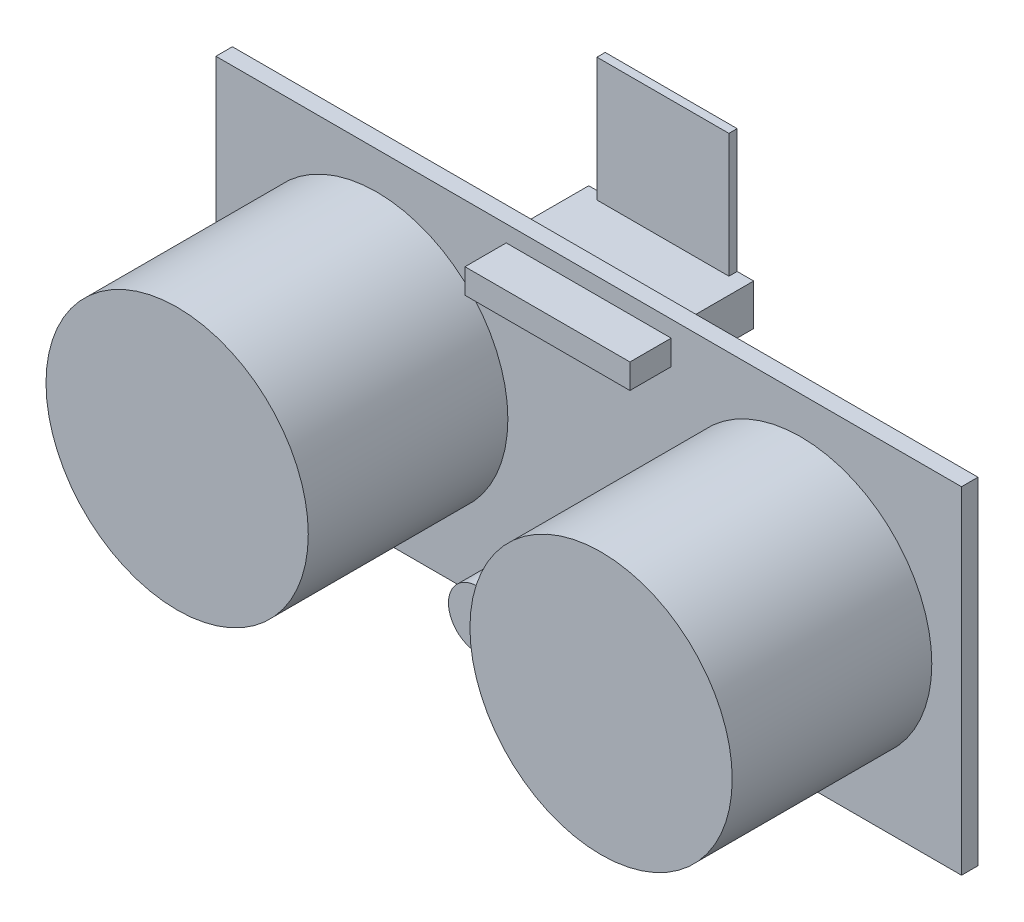
SolidWorks part; units mm, degrees
ref_plane "Plano frontal" through (0, 0, 0) normal (0, 0, 1) x (1, 0, 0)
ref_plane "Plano superior" through (0, 0, 0) normal (0, 1, 0) x (1, 0, 0)
ref_plane "Plano direito" through (0, 0, 0) normal (1, 0, 0) x (0, 0, -1)
sketch "Esboço1" plane through (0, 0, 0) normal (0, 0, 1) x (1, 0, 0)
  line L1 (0, 0) -> (45.2, 0)
  line L2 (0, 0) -> (0, 20.4)
  line L3 (0, 20.4) -> (45.2, 20.4)
  line L4 (45.2, 0) -> (45.2, 20.4)
  dimension "D1" = 20.4
  dimension "D2" = 45.2
extrude "Ressalto-extrusão1" add sketch "Esboço1" along normal blind 1
sketch "Esboço2" plane through (0, 0, 1) normal (0, 0, 1) x (1, 0, 0)
  line L0 (22.6, 20.4) -> (22.6, 0) construction
  line L1 (45.2, 20.4) -> (0, 20.4) construction
  line L2 (0, 0) -> (45.2, 0) construction
  circle A0 centre (9.75, 10.2) radius 7.95
  circle A1 centre (35.45, 10.2) radius 7.95
  dimension "D1" = 15.9
  dimension "D2" = 12.85
  dimension "D3" = 10.2
extrude "Ressalto-extrusão2" add sketch "Esboço2" along normal blind 12.1
sketch "Esboço3" plane through (0, 0, 1) normal (0, 0, 1) x (1, 0, 0)
  line L0 (22.6, 20.4) -> (22.6, 0) construction
  line L1 (45.2, 20.4) -> (0, 20.4) construction
  line L2 (0, 0) -> (45.2, 0) construction
  line L3 (45.2, 10.2) -> (0, 10.2) construction
  line L6 (27.6, 0.5) -> (17.6, 0.5)
  line L7 (27.6, 0.5) -> (27.6, 4)
  line L8 (27.6, 4) -> (17.6, 4)
  line L9 (17.6, 0.5) -> (17.6, 4)
  line L10 (27.6, 0.5) -> (17.6, 4) construction
  line L11 (27.6, 4) -> (17.6, 0.5) construction
  line L12 (45.2, 0) -> (45.2, 20.4) construction
  line L13 (0, 20.4) -> (0, 0) construction
  point P6 (22.6, 2.25)
  dimension "D1" = 10
  dimension "D2" = 3.5
  dimension "D3" = 4
  dimension "D4" = 7.95
extrude "Ressalto-extrusão3" add sketch "Esboço3" along normal blind 3.5
fillet "Filete1" radius 1.75 4 edges at (27.6, 0.5, 2.75) (27.6, 4, 2.75) (17.6, 4, 2.75) (17.6, 0.5, 2.75)
sketch "Esboço4" plane through (0, 0, 0) normal (0, 0, -1) x (-1, 0, 0)
  line L0 (-22.6, 20.4) -> (-22.6, 0) construction
  line L1 (-45.2, 20.4) -> (0, 20.4) construction
  line L2 (0, 0) -> (-45.2, 0) construction
  line L4 (-27.6, 19.9014) -> (-17.6, 19.9014)
  line L5 (-27.6, 19.9014) -> (-27.6, 17.4014)
  line L6 (-27.6, 17.4014) -> (-17.6, 17.4014)
  line L7 (-17.6, 19.9014) -> (-17.6, 17.4014)
  line L8 (-27.6, 19.9014) -> (-17.6, 17.4014) construction
  line L9 (-27.6, 17.4014) -> (-17.6, 19.9014) construction
  point P6 (-22.6, 18.6514)
  dimension "D1" = 10
  dimension "D2" = 2.5
  dimension "D3" = 2.9986
extrude "Ressalto-extrusão4" add sketch "Esboço4" along normal blind 4
sketch "Esboço5" plane through (0, 19.9014, 0) normal (0, 1, 0) x (1, 0, 0)
  line L0 (22.6, 4) -> (22.6, 0) construction
  line L1 (17.6, 4) -> (27.6, 4) construction
  line L2 (45.2, 0) -> (0, 0) construction
  line L4 (18.6, 3.5) -> (26.6, 3.5)
  line L5 (18.6, 3.5) -> (18.6, 4)
  line L6 (18.6, 4) -> (26.6, 4)
  line L7 (26.6, 3.5) -> (26.6, 4)
  line L8 (18.6, 3.5) -> (26.6, 4) construction
  line L9 (18.6, 4) -> (26.6, 3.5) construction
  point P6 (22.6, 3.75)
  dimension "D1" = 8
  dimension "D2" = 0.5
  dimension "D3" = 0
extrude "Ressalto-extrusão5" add sketch "Esboço5" along normal blind 7.5
sketch "Esboço7" plane through (0, 0, 1) normal (0, 0, 1) x (1, 0, 0)
  line L0 (45.2, 20.4) -> (0, 20.4) construction
  line L1 (17.6, 19.4) -> (27.6, 19.4)
  line L2 (17.6, 19.4) -> (17.6, 17.9)
  line L3 (17.6, 17.9) -> (27.6, 17.9)
  line L4 (27.6, 19.4) -> (27.6, 17.9)
  line L5 (17.6, 19.4) -> (27.6, 17.9) construction
  line L6 (17.6, 17.9) -> (27.6, 19.4) construction
  line L7 (0, 20.4) -> (0, 0) construction
  line L8 (45.2, 0) -> (45.2, 20.4) construction
  point P0 (22.6, 18.65)
  dimension "D1" = 10
  dimension "D2" = 1.5
  dimension "D3" = 2.5
  dimension "D4" = 45.2
  dimension "D5" = 22.6
extrude "Ressalto-extrusão6" add sketch "Esboço7" along normal blind 2.5
